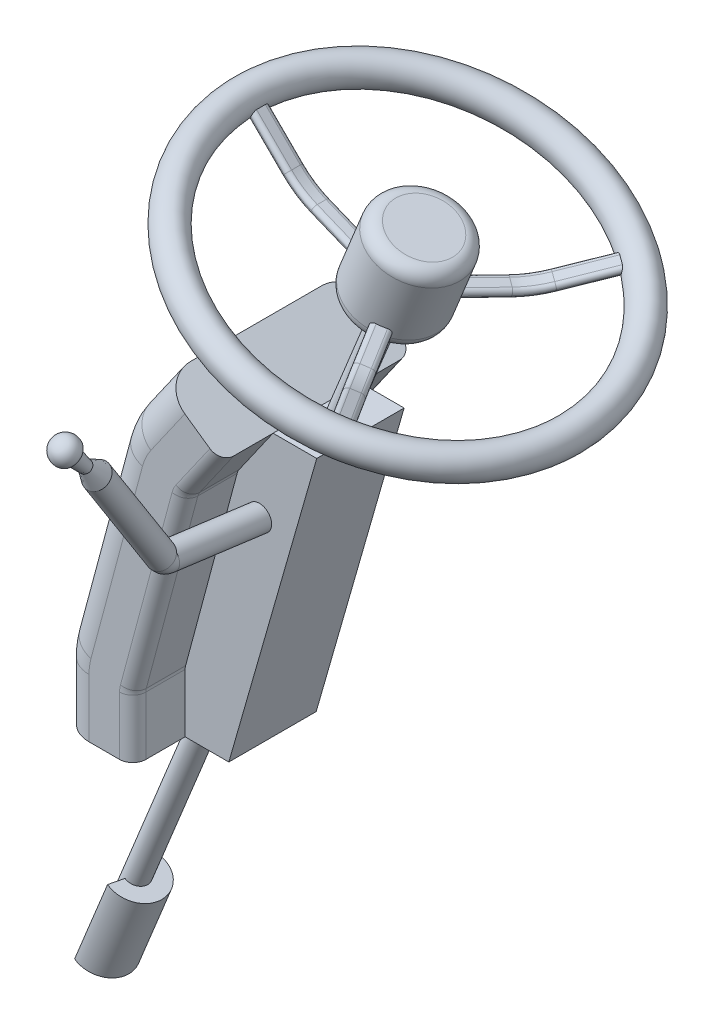
SolidWorks part; units mm, degrees
ref_plane "Front Plane" through (0, 0, 0) normal (0, 0, 1) x (1, 0, 0)
ref_plane "Top Plane" through (0, 0, 0) normal (0, 1, 0) x (1, 0, 0)
ref_plane "Right Plane" through (0, 0, 0) normal (1, 0, 0) x (0, 0, -1)
sketch "Sketch1" plane through (0, 0, 0) normal (0, 0, 1) x (1, 0, 0)
  line L0 (0, 0) -> (0, 66.8348)
  line L1 (3.4074, 92.7167) -> (62.4236, 312.9681)
  line L2 (77.101, 344.4439) -> (116.0018, 400)
  arc A0 (62.4236, 312.9681) -> (77.101, 344.4439) centre (159.0162, 287.0862) cw
  arc A1 (0, 66.8348) -> (3.4074, 92.7167) centre (100, 66.8348) cw
  point P8 (66.9873, 330)
  point P11 (0, 80)
  dimension "D6" = 100
  dimension "D1" = 250
  dimension "D2" = 400
  dimension "D3" = 15
  dimension "D4" = 20
  dimension "D5" = 80
extrude "Extrude-Thin1" add sketch "Sketch1" along normal mid plane 220 thin
fillet "Fillet1" radius 35 10 edges at (0, 33.4174, -110) (0.8555, 79.8874, -110) (96.5514, 372.2219, -110) (68.3854, 329.348, -110) (0, 33.4174, 110) (0.8555, 79.8874, 110) (96.5514, 372.2219, 110) (68.3854, 329.348, 110) (32.9155, 202.8424, -110) (32.9155, 202.8424, 110)
fillet "Fillet2" radius 15 10 edges at (85, 33.4174, -110) (85.1283, 68.7926, -110) (166.1793, 323.4679, -110) (145.4216, 293.4255, -110) (85, 33.4174, 110) (85.1283, 68.7926, 110) (166.1793, 323.4679, 110) (145.4216, 293.4255, 110) (115.0192, 180.8428, -110) (115.0192, 180.8428, 110)
sketch "Sketch2" plane through (0, 0, 0) normal (0, 0, 1) x (1, 0, 0)
  line L0 (85, 66.8348) -> (85, 0) construction
  line L1 (144.5273, 290.9685) -> (85.5111, 70.717) construction
  line L2 (185.6297, 351.246) -> (146.7289, 295.6899) construction
  line L3 (185.6297, 351.246) -> (146.7289, 295.6899)
  line L4 (144.5273, 290.9685) -> (85.5111, 70.717)
  line L5 (85, 66.8348) -> (85, 0)
  line L6 (85, 0) -> (135, 0)
  line L7 (135, 0) -> (235.6297, 351.246)
  line L8 (235.6297, 351.246) -> (185.6297, 351.246)
  arc A0 (85.5111, 70.717) -> (85, 66.8348) centre (100, 66.8348) ccw construction
  arc A1 (146.7289, 295.6899) -> (144.5273, 290.9685) centre (159.0162, 287.0862) ccw construction
  arc A2 (85.5111, 70.717) -> (85, 66.8348) centre (100, 66.8348) ccw
  arc A3 (146.7289, 295.6899) -> (144.5273, 290.9685) centre (159.0162, 287.0862) ccw
  dimension "D1" = 50
extrude "Boss-Extrude1" add sketch "Sketch2" along normal mid plane 100
ref_plane "Plane1" through (156.3219, 383.5677, 0) normal (-0.3774, -0.926, 0) x (-0.926, 0.3774, 0)
sketch "Sketch3" plane through (156.3219, 383.5677, 0) normal (-0.3774, -0.926, 0) x (-0.926, 0.3774, 0)
  line L0 (-39.339, -50) -> (-85.6413, 50) construction
  circle A0 centre (-62.4901, 0) radius 12.5
  dimension "D1" = 25
extrude "Boss-Extrude2" add sketch "Sketch3" along normal blind 729 and the other way blind 150 contours A0
ref_axis "Axis1" through (274.0994, 506.9818, 0) along (-0.3774, -0.926, 0)
sketch "Sketch4" plane through (0, 0, 0) normal (0, 0, 1) x (1, 0, 0)
  line L0 (93.5513, 409.1496) -> (219.0924, 357.9857) construction
  line L1 (274.0994, 506.9818) -> (208.7071, 346.5284) construction
  line L2 (270.8018, 498.8905) -> (224.4995, 517.7609)
  line L3 (270.8018, 498.8905) -> (308.5426, 591.4952)
  line L4 (224.4995, 517.7609) -> (262.2402, 610.3656)
  line L5 (308.5426, 591.4952) -> (262.2402, 610.3656)
  line L6 (282.3774, 494.1729) -> (259.2262, 503.6081) construction
  circle A0 centre (104.4628, 620.6744) radius 17.5
  dimension "D1" = 35
  dimension "D2" = 200
  dimension "D3" = 200
  dimension "D4" = 100
  dimension "D5" = 50
revolve "Revolve1" add sketch "Sketch4" angle 360 about axis through (274.0994, 506.9818, 0) along (-0.3774, -0.926, 0)
fillet "Fillet3" radius 15 2 edges at (224.4995, 517.7609, 0) (262.2402, 610.3656, 0)
sketch "Sketch5" plane through (0, 0, 0) normal (0, 0, 1) x (1, 0, 0)
  line L0 (104.4628, 620.6744) -> (154.8088, 570.6744)
  line L1 (187.5344, 549.0238) -> (243.0894, 526.3825)
  line L2 (322.7653, 493.9108) -> (230.1606, 531.6516) construction
  arc A0 (97.8581, 604.4686) -> (111.0674, 636.8802) centre (104.4628, 620.6744) ccw construction
  arc A1 (154.8088, 570.6744) -> (187.5344, 549.0238) centre (225.2752, 641.6285) ccw
  point P13 (169.0056, 556.5751)
  dimension "D2" = 100
  dimension "D3" = 50
  dimension "D1" = 80
extrude "Extrude-Thin2" add sketch "Sketch5" along normal mid plane 20 thin
fillet "Fillet4" radius 5 12 edges at (135.9332, 589.4202, -10) (170.0992, 558.2282, -10) (141.8928, 597.5952, -10) (175.6168, 566.5682, -10) (135.9332, 589.4202, 10) (215.3119, 537.7031, 10) (141.8928, 597.5952, 10) (219.086, 546.9636, 10) (215.3119, 537.7031, -10) (219.086, 546.9636, -10) (170.0992, 558.2282, 10) (175.6168, 566.5682, 10)
pattern_circular "CirPattern1" count 3 over 360 about axis through (57.8688, -23.5843, 0) along (0.3774, 0.926, 0) of "Fillet4", "Extrude-Thin2"
sketch "Sketch6" plane through (-118.8084, -291.5207, 0) normal (-0.3774, -0.926, 0) x (-0.926, 0.3774, 0)
  line L0 (-62.4901, 20) -> (-62.4901, -20) construction
  line L1 (-62.4901, 0) -> (-57.2807, 29.5442) construction
  line L2 (-92.4901, 0) -> (-42.4901, 0) construction
  line L3 (-62.4901, 0) -> (-57.2807, -29.5442) construction
  line L4 (-62.4901, 0) -> (-57.2807, 29.5442)
  line L5 (-57.2807, -29.5442) -> (-62.4901, 0)
  arc A0 (-57.2807, 29.5442) -> (-57.2807, -29.5442) centre (-62.4901, 0) ccw
  dimension "D1" = 60
  dimension "D2" = 100
extrude "Boss-Extrude3" add sketch "Sketch6" against normal blind 100 from offset 10 contours A0 L5 L4 offset against normal yes
sketch "Sketch7" plane through (0, 0, 50) normal (0, 0, 1) x (1, 0, 0)
  circle A0 centre (170, 260) radius 14
  dimension "D1" = 28
  dimension "D2" = 170
  dimension "D3" = 260
ref_plane "Plane2" through (170, 0, 0) normal (1, 0, 0) x (0, 0, -1)
sketch "Sketch8" plane through (170, 0, 0) normal (1, 0, 0) x (0, 0, -1)
  line L0 (-50, 260) -> (-155.3775, 274)
  line L1 (-50, 274) -> (-50, 246) construction
  line L2 (-162.5008, 278.5499) -> (-236.2491, 394.6141)
  line L4 (-50, 260) -> (-211.9276, 260) construction
  arc A0 (-155.3775, 274) -> (-162.5008, 278.5499) centre (-154.0606, 283.9129) cw
  point P6 (-102.6888, 267)
  point P9 (-160, 274.6141)
  dimension "D5" = 10
  dimension "D1" = 110
  dimension "D2" = 120
  dimension "D3" = 130
  dimension "D4" = 14
sweep "Sweep1" add profiles "Sketch7" path "Sketch8"
sketch "Sketch10" plane through (170, 0, 0) normal (1, 0, 0) x (0, 0, -1)
  line L0 (-225.5245, 403.6131) -> (-246.9737, 385.6151) construction
  line L1 (-225.5245, 403.6131) -> (-246.9737, 385.6151) construction
  line L2 (-236.2491, 394.6141) -> (-318.4383, 492.5635) construction
  line L3 (-225.5245, 403.6131) -> (-243.9566, 414.2549)
  line L4 (-243.9566, 414.2549) -> (-261.2491, 438.7696)
  line L5 (-261.2491, 438.7696) -> (-258.8539, 444.2708)
  line L6 (-236.2491, 394.6141) -> (-225.5245, 403.6131)
  line L7 (-281.887, 449.0033) -> (-236.2491, 394.6141)
  arc A0 (-258.8539, 444.2708) -> (-281.887, 449.0033) centre (-272.2452, 437.5126) ccw
  dimension "D3" = 30
  dimension "D1" = 56
  dimension "D2" = 70
  dimension "D4" = 30
  dimension "D5" = 6
  dimension "D6" = 20
  dimension "D7" = 25
revolve "Revolve2" add sketch "Sketch10" angle 360 about L2
